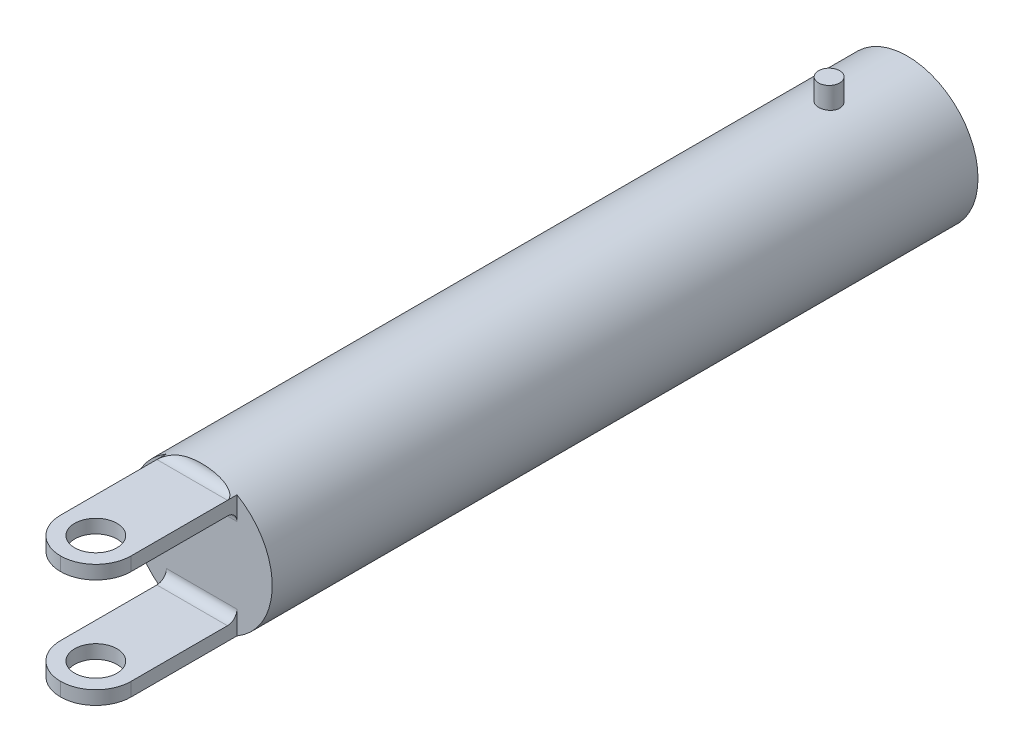
SolidWorks part; units mm, degrees
ref_plane "Front Plane" through (0, 0, 0) normal (1, 0, 0) x (0, 1, 0)
ref_plane "Top Plane" through (0, 0, 0) normal (0, 0, 1) x (0, 1, 0)
ref_plane "Right Plane" through (0, 0, 0) normal (0, 1, 0) x (-1, 0, 0)
sketch "Sketch1" plane through (0, 0, 0) normal (0, 0, 1) x (0, 1, 0)
  circle A0 centre (0, 0) radius 10
  dimension "D1" = 20
extrude "Boss-Extrude1" add sketch "Sketch1" along normal blind 100
sketch "Sketch3" plane through (0, 0, 100) normal (0, 0, 1) x (1, 0, 0)
  line L0 (14.1124, 0) -> (-15.8793, 0) construction
  line L1 (5, 8.6603) -> (-5, 8.6603)
  line L2 (5, 8.6603) -> (5, 6.7306)
  line L3 (5, 6.7306) -> (-5, 6.7306)
  line L4 (-5, 8.6603) -> (-5, 6.7306)
  line L5 (5, -6.7306) -> (-5, -6.7306)
  line L6 (-5, -8.6603) -> (-5, -6.7306)
  line L7 (5, -8.6603) -> (-5, -8.6603)
  line L8 (5, -8.6603) -> (5, -6.7306)
  circle A0 centre (0, 0) radius 10 construction
  circle A1 centre (0, 0) radius 10
  point P12 (0, 0)
  point P13 (0, 0)
  point P14 (-5, -8.6603)
  dimension "D1" = 10
extrude "Boss-Extrude3" add sketch "Sketch3" along normal blind 20 contours L1 L4 L3 L2 | L7 L8 L5 L6 region at (0, 7.6954, 100) region at (0, -7.6954, 100)
sketch "Sketch4" plane through (0, -8.6603, 0) normal (0, -1, 0) x (1, 0, 0)
  line L0 (5, 120) -> (-5, 120) construction
  circle A0 centre (0, 115) radius 3
  dimension "D1" = 5
  dimension "D2" = 6
extrude "Cut-Extrude1" cut sketch "Sketch4" against normal through all
fillet "Fillet2" radius 5 4 edges at (-5, 7.6954, 120) (5, 7.6954, 120) (-5, -7.6954, 120) (5, -7.6954, 120)
fillet "Fillet3" radius 1.35 4 edges at (0, -6.7306, 100) (0, 6.7306, 100) (0, 8.6603, 100) (0, -8.6603, 100)
sketch "Sketch7" plane through (0, 0, 0) normal (0, 1, 0) x (-1, 0, 0)
  circle A0 centre (0, 11.0985) radius 1.5
  dimension "D1" = 3
extrude "Boss-Extrude4" add sketch "Sketch7" along normal blind 13
